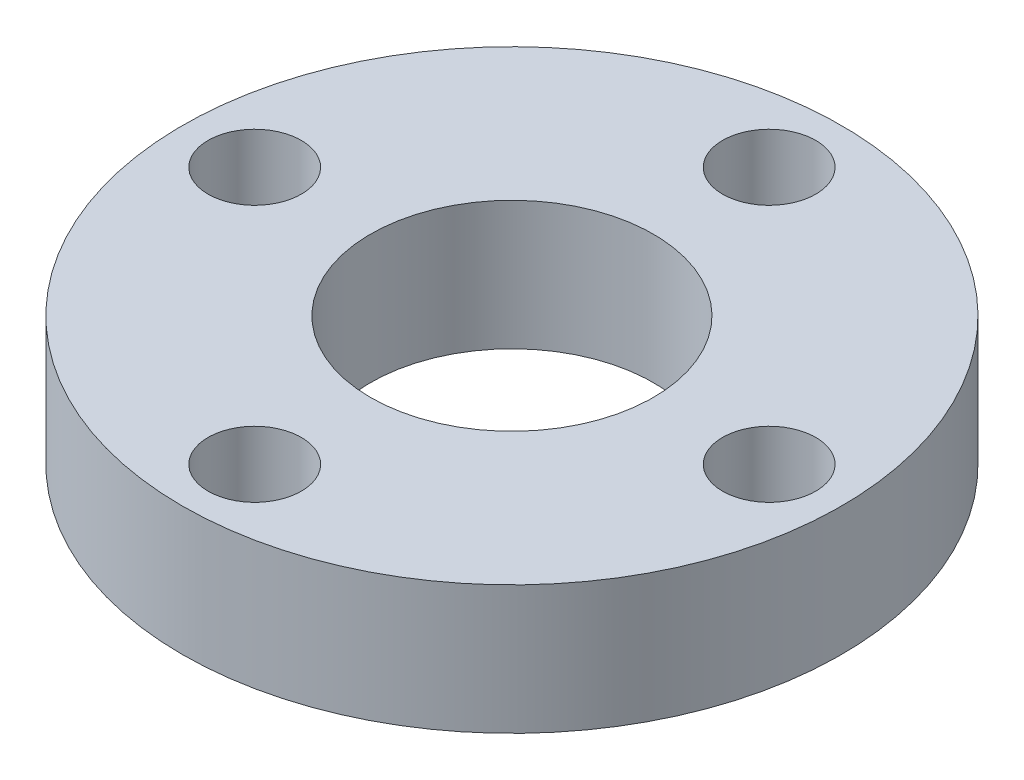
SolidWorks part; units mm, degrees
ref_plane "Front Plane" through (0, 0, 0) normal (0, 0, 1) x (1, 0, 0)
ref_plane "Top Plane" through (0, 0, 0) normal (0, 1, 0) x (1, 0, 0)
ref_plane "Right Plane" through (0, 0, 0) normal (1, 0, 0) x (0, 0, -1)
sketch "Sketch1" plane through (0, 0, 0) normal (0, 1, 0) x (1, 0, 0)
  circle A0 centre (0, 0) radius 10.25
  circle A1 centre (0, 0) radius 4.4
  circle A2 centre (0, 0) radius 8
  circle A3 centre (0, 8) radius 1.45
  circle A4 centre (8, 0) radius 1.45
  circle A5 centre (0, -8) radius 1.45
  circle A6 centre (-8, 0) radius 1.45
  point P16 (0, 0)
  dimension "D1" = 20.5
  dimension "D2" = 8.8
  dimension "D3" = 2.9
  dimension "D4" = 4
extrude "Boss-Extrude1" add sketch "Sketch1" along normal blind 4 contours A0 A6 A2 A3 A4 A5 | A6 A2 A5 A4 A3 A1 region at (-9.9601, 0, 0) region at (6.3274, 0, 0)
